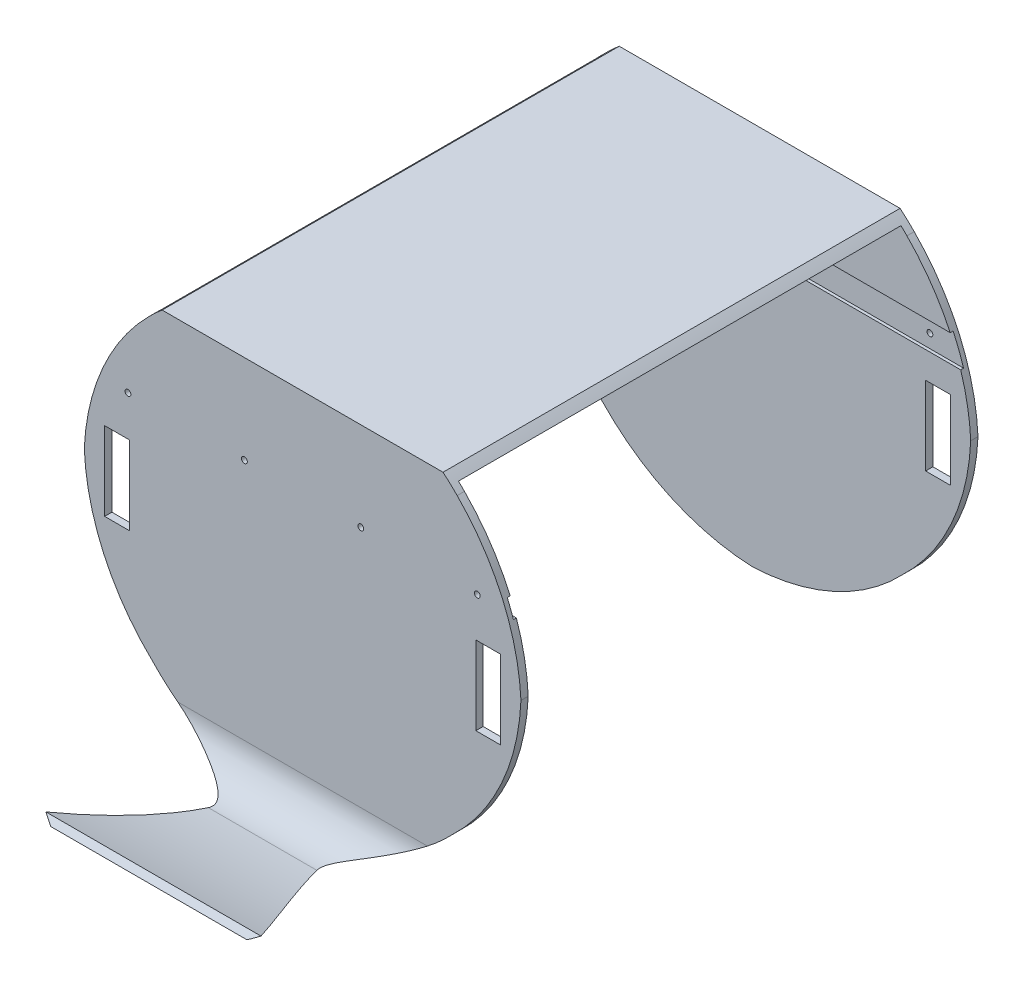
SolidWorks part; units mm, degrees
ref_plane "Front Plane" through (0, 0, 0) normal (0, 0, 1) x (1, 0, 0)
ref_plane "Top Plane" through (0, 0, 0) normal (0, 1, 0) x (1, 0, 0)
ref_plane "Right Plane" through (0, 0, 0) normal (1, 0, 0) x (0, 0, -1)
sketch "Sketch1" plane through (0, 0, 0) normal (1, 0, 0) x (0, 0, -1)
  line L0 (-152, 0) -> (152, 0) construction
  line L1 (-152, 0) -> (-152, 254)
  line L2 (-152, 254) -> (152, 254)
  line L3 (152, 254) -> (152, 0)
  line L5 (-157, 31.1836) -> (-157, 259)
  line L6 (-157, 259) -> (157, 259)
  line L7 (157, 259) -> (157, 0)
  line L8 (157, 0) -> (152, 0)
  line L9 (-262.642, 19.1007) -> (-259.4281, 22.931)
  line L10 (-157, 145) -> (-262.642, 19.1007) construction
  arc A0 (-152, 0) -> (-262.642, 19.1007) centre (-152, 330) cw
  arc A3 (-259.4281, 22.931) -> (-184.4973, 6.3086) centre (-152, 330) ccw
  arc A4 (-157, 31.1836) -> (-184.4973, 6.3086) centre (-182, 31.1836) cw
  point P3 (-168.2848, 145.1156)
  point P4 (0, 0)
  point P18 (0, 0)
  dimension "D6" = 25
  dimension "D9" = 330
  dimension "D1" = 304
  dimension "D2" = 5
  dimension "D3" = 5
  dimension "D4" = 5
  dimension "D5" = 5
  dimension "D7" = 254
  dimension "D8" = 50
  dimension "D10" = 145
extrude "Boss-Extrude1" add sketch "Sketch1" along normal blind 150 and the other way blind 150
sketch "Sketch2" plane through (0, 0, 0) normal (0, 0, 1) x (1, 0, 0)
  line L1 (0, 150) -> (0, 0) construction
  line L2 (0, 150) -> (150, 150) construction
  line L3 (0, 150) -> (103.1245, 46.8755) construction
  line L4 (0, 150) -> (56.5109, 13.5707) construction
  line L5 (0, 150) -> (136.4293, 93.4891) construction
  line L6 (56.5109, 13.5707) -> (0, 13.5707) construction
  line L7 (136.4293, 93.4891) -> (136.4293, 150) construction
  line L8 (0, 150) -> (131.304, 216.3149) construction
  line L9 (0, 150) -> (0, 295.5) construction
  line L10 (0, 150) -> (106.1806, 249.9895) construction
  arc A0 (0, 0) -> (103.1245, 46.8755) centre (-6.3266, 150.7909) ccw
  arc A1 (150, 150) -> (103.1245, 46.8755) centre (-0.7909, 156.3266) cw
  arc A2 (106.1806, 249.9895) -> (150, 150) centre (-2.2818, 142.8605) cw
  arc A3 (106.1806, 249.9895) -> (0, 295.5) centre (-2.7988, 142.3499) ccw
  arc A4 (0, 0) -> (-103.1245, 46.8755) centre (6.3266, 150.7909) cw
  arc A5 (-150, 150) -> (-103.1245, 46.8755) centre (0.7909, 156.3266) ccw
  arc A6 (-106.1806, 249.9895) -> (-150, 150) centre (2.2818, 142.8605) ccw
  arc A7 (-106.1806, 249.9895) -> (0, 295.5) centre (2.7988, 142.3499) cw
  dimension "D1" = 150
  dimension "D2" = 22.5
  dimension "D3" = 22.5
  dimension "D4" = 145.84
  dimension "D5" = 147.67
  dimension "D6" = 147.1
  dimension "D7" = 26.796
  dimension "D8" = 145.5
  dimension "D9" = 43.28
  dimension "D10" = 145.85
extrude "Cut-Extrude1" cut sketch "Sketch2" against normal through all both and the other way through all flip side to cut contours A7 A6 A5 A4 A0 A1 A2 A3
sketch "Sketch3" plane through (0, 0, 0) normal (1, 0, 0) x (0, 0, -1)
  line L0 (-152, 198) -> (152, 198) construction
  line L1 (-154, 192.5) -> (-150, 192.5)
  line L2 (-154, 192.5) -> (-154, 203.5)
  line L3 (-154, 203.5) -> (-150, 203.5)
  line L4 (-150, 192.5) -> (-150, 203.5)
  line L5 (-154, 192.5) -> (-150, 203.5) construction
  line L6 (-154, 203.5) -> (-150, 192.5) construction
  line L7 (150, 188.75) -> (154, 188.75)
  line L8 (150, 188.75) -> (150, 207.25)
  line L9 (150, 207.25) -> (154, 207.25)
  line L10 (154, 188.75) -> (154, 207.25)
  line L11 (150, 188.75) -> (154, 207.25) construction
  line L12 (150, 207.25) -> (154, 188.75) construction
  line L13 (0, 0) -> (0, 198) construction
  point P0 (-152, 198)
  point P5 (152, 198)
  dimension "D1" = 304
  dimension "D2" = 4
  dimension "D3" = 198
  dimension "D4" = 11
extrude "Cut-Extrude2" cut sketch "Sketch3" against normal through all both and the other way through all
sketch "Sketch4" plane through (0, 0, 0) normal (0, 0, 1) x (1, 0, 0)
  line L0 (0, 0) -> (0, 259) construction
  line L1 (-96.4763, 259) -> (96.4763, 259) construction
  line L2 (-120, 198) -> (120, 198) construction
  circle A0 centre (-120, 198) radius 2
  circle A1 centre (120, 198) radius 2
  circle A2 centre (40, 198) radius 2
  circle A3 centre (-40, 198) radius 2
  point P8 (0, 198)
  dimension "D3" = 4
  dimension "D1" = 240
  dimension "D2" = 80
  dimension "D4" = 198
extrude "Cut-Extrude3" cut sketch "Sketch4" against normal through all both and the other way through all
sketch "Sketch6" plane through (0, 0, 0) normal (0, 0, 1) x (1, 0, 0)
  line L0 (-127.5, 143.5) -> (127.5, 143.5) construction
  line L1 (-136, 116.5) -> (-119, 116.5)
  line L2 (-136, 116.5) -> (-136, 170.5)
  line L3 (-136, 170.5) -> (-119, 170.5)
  line L4 (-119, 116.5) -> (-119, 170.5)
  line L5 (-136, 116.5) -> (-119, 170.5) construction
  line L6 (-136, 170.5) -> (-119, 116.5) construction
  line L7 (119, 170.5) -> (136, 170.5)
  line L8 (119, 170.5) -> (119, 116.5)
  line L9 (119, 116.5) -> (136, 116.5)
  line L10 (136, 170.5) -> (136, 116.5)
  line L11 (119, 170.5) -> (136, 116.5) construction
  line L12 (119, 116.5) -> (136, 170.5) construction
  line L13 (0, 143.5) -> (0, 0) construction
  point P0 (-127.5, 143.5)
  point P5 (127.5, 143.5)
  point P15 (127.5, 116.5)
  dimension "D1" = 272
  dimension "D2" = 17
  dimension "D3" = 54
  dimension "D4" = 116.5
extrude "Cut-Extrude4" cut sketch "Sketch6" against normal through all both and the other way through all
